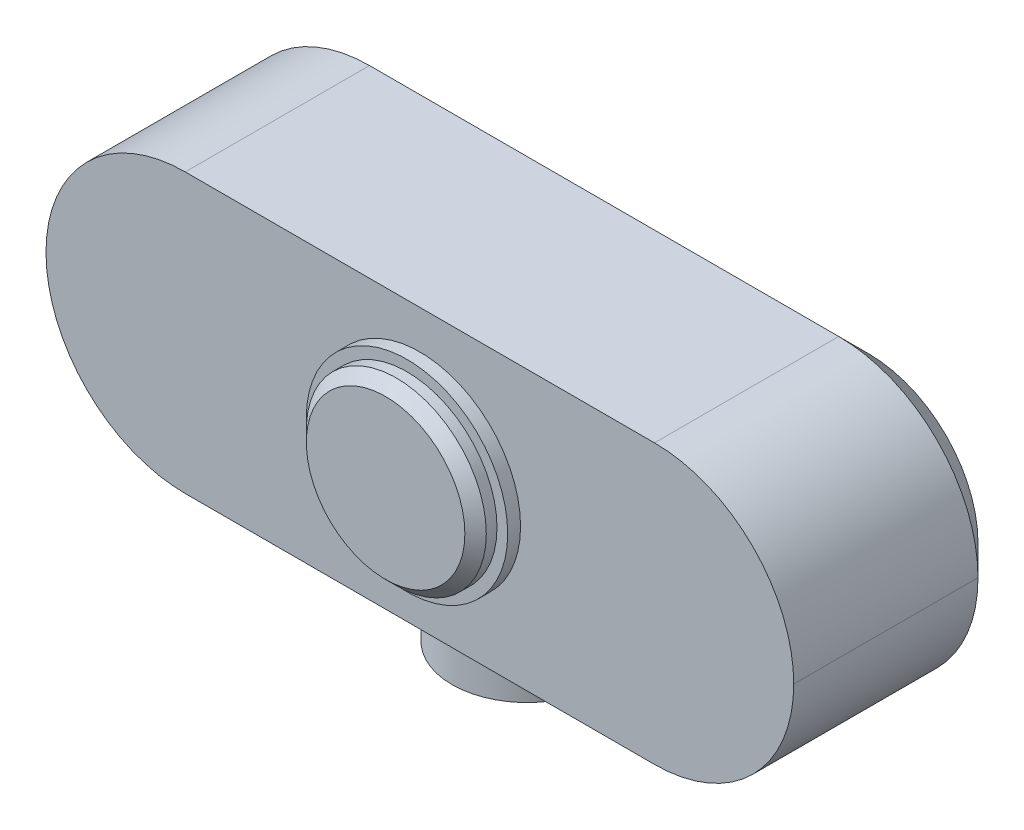
SolidWorks part; units mm, degrees
ref_plane "Front Plane" through (0, 0, 0) normal (0, 0, 1) x (1, 0, 0)
ref_plane "Top Plane" through (0, 0, 0) normal (0, 1, 0) x (1, 0, 0)
ref_plane "Right Plane" through (0, 0, 0) normal (1, 0, 0) x (0, 0, -1)
sketch "Sketch1" plane through (0, 0, 0) normal (0, 0, 1) x (1, 0, 0)
  line L1 (34.9, -13) -> (-34.9, -13)
  line L2 (34.9, -13) -> (34.9, 13)
  line L3 (34.9, 13) -> (-34.9, 13)
  line L4 (-34.9, -13) -> (-34.9, 13)
  line L5 (34.9, -13) -> (-34.9, 13) construction
  line L6 (34.9, 13) -> (-34.9, -13) construction
  point P0 (0, 0)
  dimension "D1" = 69.8
  dimension "26" = 26
extrude "Boss-Extrude1" add sketch "Sketch1" along normal blind 20
fillet "Fillet1" radius 13 4 edges at (-34.9, -13, 10) (-34.9, 13, 10) (34.9, -13, 10) (34.9, 13, 10)
sketch "Sketch2" plane through (0, 0, 20) normal (0, 0, 1) x (1, 0, 0)
  circle A0 centre (0, 0) radius 9.4
  dimension "D1" = 18.8
extrude "Boss-Extrude2" add sketch "Sketch2" along normal blind 1.2
sketch "Sketch3" plane through (0, 0, 21.2) normal (0, 0, 1) x (1, 0, 0)
  circle A0 centre (0, 0) radius 8.4
  dimension "D1" = 16.8
extrude "Boss-Extrude3" add sketch "Sketch3" along normal blind 2
chamfer "Chamfer1" distance 1 angle 45 1 edges at (8.4, 0, 23.2)
sketch "Sketch4" plane through (0, -13, 0) normal (0, -1, 0) x (1, 0, 0)
  line L0 (0, 0) -> (0, 20) construction
  line L1 (-21.9, 20) -> (21.9, 20) construction
  circle A0 centre (0, 10) radius 7
  circle A1 centre (0, 10) radius 5
  dimension "D1" = 14
  dimension "D2" = 10
extrude "Boss-Extrude4" add sketch "Sketch4" along normal blind 6
sketch "Sketch5" plane through (0, 0, 0) normal (0, 0, -1) x (-1, 0, 0)
  line L0 (-32.147, -8) -> (32.147, -8) construction
  line L1 (21.9, -13) -> (-21.9, -13) construction
  line L2 (-18.9, 13) -> (-18.9, -13) construction
  line L3 (-21.9, 13) -> (21.9, 13) construction
  arc A0 (-34.9, 0) -> (-21.9, -13) centre (-21.9, 0) ccw construction
  arc A1 (21.9, -13) -> (34.9, 0) centre (21.9, 0) ccw construction
  circle A2 centre (-18.9, -8) radius 1.75
  dimension "D3" = 3.5
  dimension "D1" = 5
  dimension "D2" = 16
extrude "Boss-Extrude5" add sketch "Sketch5" along normal blind 5
chamfer "Chamfer2" distance 2.8 angle 45 6 edges at (-31.0924, -9.1924, 0) (-31.0924, 9.1924, 0) (0, -13, 0) (0, 13, 0) (31.0924, -9.1924, 0) (31.0924, 9.1924, 0)
sketch "Sketch6" plane through (0, 0, 0) normal (0, 0, -1) x (-1, 0, 0)
  line L0 (-21.4, -10.2) -> (-21.4, -8)
  line L1 (-21.9, -10.2) -> (21.9, -10.2) construction
  line L2 (-18.9, -8) -> (-18.9, -10.2) construction
  line L3 (-16.4, -8) -> (-16.4, -10.2)
  line L4 (-21.4, -10.2) -> (-16.4, -10.2)
  arc A0 (-21.4, -8) -> (-16.4, -8) centre (-18.9, -8) cw
  circle A2 centre (-18.9, -8) radius 1.75
  circle A3 centre (-18.9, -8) radius 1.75 construction
  dimension "D2" = 2.5
  dimension "D1" = 5
extrude "Cut-Extrude1" cut sketch "Sketch6" against normal blind 1
